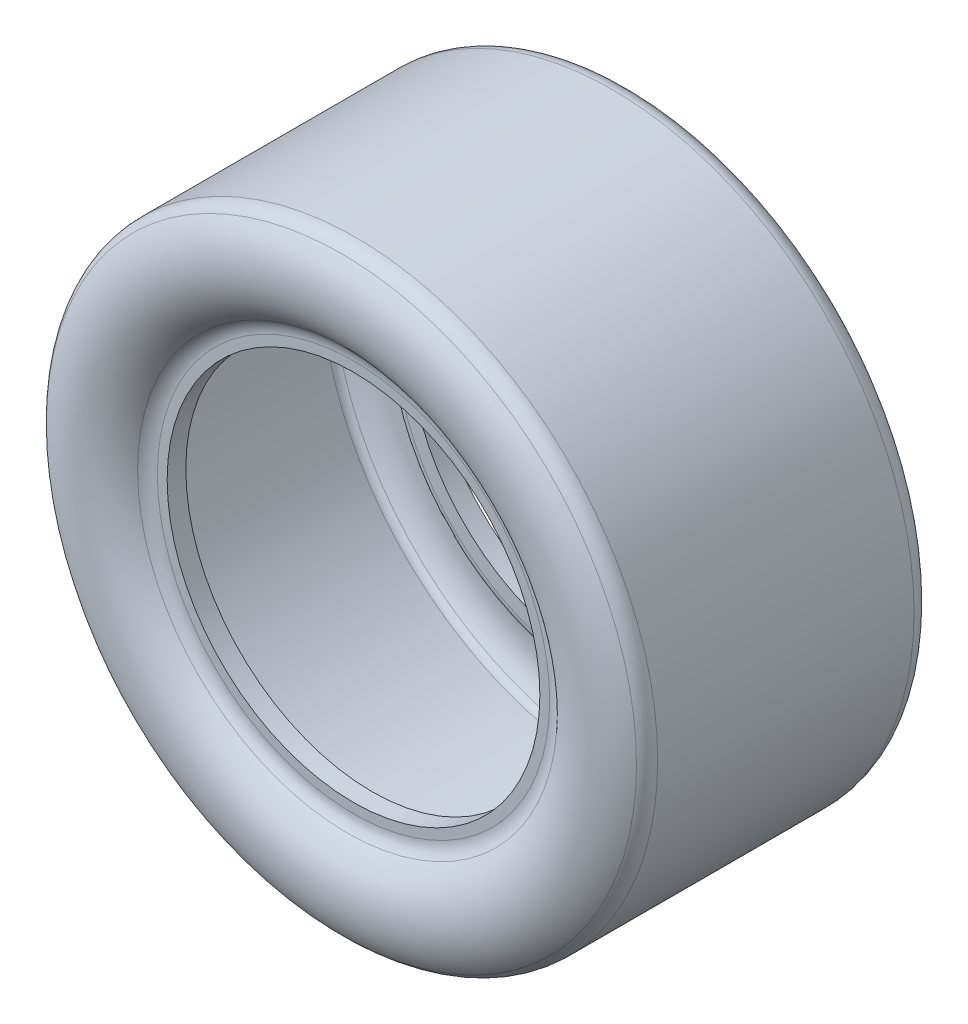
SolidWorks part; units mm, degrees
material "Tire Rubber"
ref_plane "X-Z Datum" through (0, 0, 0) normal (0, 0, 1) x (1, 0, 0)
ref_plane "X-Y Datum" through (0, 0, 0) normal (0, 1, 0) x (1, 0, 0)
ref_plane "Y-Z Plane" through (0, 0, 0) normal (1, 0, 0) x (0, 0, -1)
sketch "Sketch1" plane through (0, 0, 0) normal (1, 0, 0) x (0, 0, -1)
  line L0 (0, 0) -> (-132272.0706, 0) construction
  line L1 (-92.71, 205.74) -> (92.71, 205.74)
  line L2 (0, 0) -> (0, -132272.0706) construction
  line L4 (-88.9, 127) -> (-88.9, 139.7)
  line L5 (88.9, 127) -> (88.9, 139.7)
  line L6 (-88.9, 127) -> (-76.2, 127)
  line L8 (76.2, 127) -> (88.9, 127)
  line L9 (-76.2, 127) -> (-76.2, 136.7746)
  line L10 (76.2, 127) -> (76.2, 136.7746)
  line L11 (-86.5663, 197.8025) -> (86.5663, 197.8025)
  arc A2 (-92.71, 205.74) -> (-88.9, 139.7) centre (-64.4017, 174.2433) ccw
  arc A3 (92.71, 205.74) -> (88.9, 139.7) centre (64.4017, 174.2433) cw
  arc A4 (-91.5819, 195.3468) -> (-80.4384, 143.7974) centre (-64.4017, 174.2433) ccw
  arc A5 (-86.5663, 197.8025) -> (-91.5819, 195.3468) centre (-86.5663, 191.4525) ccw
  arc A6 (-76.2, 136.7746) -> (-80.4384, 143.7974) centre (-84.1375, 136.7746) ccw
  arc A7 (91.5819, 195.3468) -> (80.4384, 143.7974) centre (64.4017, 174.2433) cw
  arc A8 (86.5663, 197.8025) -> (91.5819, 195.3468) centre (86.5663, 191.4525) cw
  arc A9 (80.4384, 143.7974) -> (76.2, 136.7746) centre (84.1375, 136.7746) ccw
  point P7 (-106.68, 171.8041)
  dimension "D4" = 213.36
  dimension "D9" = 7.9375
  dimension "D10" = 6.35
  dimension "D11" = 7.9375
  dimension "D12" = 7.9375
  dimension "D1" = 185.42
  dimension "D2" = 411.48
  dimension "D3" = 12.7
  dimension "D5" = 177.8
  dimension "D6" = 254
  dimension "D7" = 12.7
  dimension "D8" = 7.9375
revolve "Revolve1" add sketch "Sketch1" angle 360 about L0
fillet "Fillet1" radius 12.7 4 edges at (-139.7, 0, -88.9) (-139.7, 0, 88.9) (-205.74, 0, -92.71) (-205.74, 0, 92.71)
ref_axis "Axis1" [suppressed] through (0, 0, 87.3303) along (0, 0, -1)
sketch "Sketch2" plane through (0, 0, 0) normal (0, 0, 1) x (1, 0, 0)
  circle A0 centre (0, 0) radius 205.74
  dimension "D1" = 411.48
extrude "Boss-Extrude1" [suppressed] add sketch "Sketch2" along normal mid plane 185.42
fillet "Fillet2" [suppressed] radius 25.4
sketch "Sketch3" plane through (0, 0, 0) normal (1, 0, 0) x (0, 0, -1)
  line L0 (0, 0) -> (0, 170833.7536) construction
  line L1 (0, 0) -> (-170833.7536, 0) construction
  line L2 (106.68, 205.74) -> (-106.68, 205.74)
  line L3 (-106.68, 205.74) -> (-106.68, 0)
  line L4 (106.68, 205.74) -> (106.68, 0)
  line L5 (106.68, 0) -> (-106.68, 0)
  point P7 (0, 205.74)
  dimension "D1" = 213.36
  dimension "D2" = 411.48
revolve "Revolve2" [suppressed] add sketch "Sketch3" angle 360 about L1
move or copy body "Body-Move/Copy2" [suppressed] bodies to move or copy 101
move or copy body "Body-Move/Copy1" [suppressed] bodies to move or copy 101
